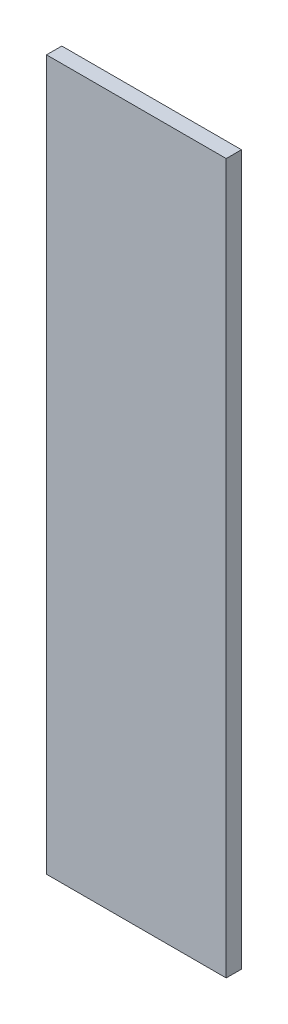
SolidWorks part; units mm, degrees
material "ABS"
ref_plane "Front Plane" through (0, 0, 0) normal (0, 0, 1) x (1, 0, 0)
ref_plane "Top Plane" through (0, 0, 0) normal (0, 1, 0) x (1, 0, 0)
ref_plane "Right Plane" through (0, 0, 0) normal (1, 0, 0) x (0, 0, -1)
sketch "Sketch1" plane through (0, 0, 0) normal (0, 0, 1) x (1, 0, 0)
  line L1 (-10, -39.5) -> (10, -39.5)
  line L2 (-10, -39.5) -> (-10, 39.5)
  line L3 (-10, 39.5) -> (10, 39.5)
  line L4 (10, -39.5) -> (10, 39.5)
  line L5 (-10, -39.5) -> (10, 39.5) construction
  line L6 (-10, 39.5) -> (10, -39.5) construction
  point P0 (0, 0)
  dimension "D1" = 20
  dimension "D2" = 79
extrude "Boss-Extrude1" add sketch "Sketch1" along normal blind 1.7
equation "\"smallPulleyTeeth\"= 30"
equation "\"largePulleyTeeth\"= 30"
equation "\"eighthThick\"= 3.0mm"
equation "\"sixteenthThick\" = 1.7mm"
equation "\"quarterThick\"=6.0mm"
equation "\"OD\" = 145mm"
equation "\"puckAngle\" = 60.5deg"
equation "\"puckDiam\" = 76.5mm"
equation "\"puckDist\" = 85mm"
equation "\"scoopFillet\" = 5mm"
equation "\"axlePress\" = 5.9mm"
equation "\"press\" = 0.2mm"
equation "\"wheelClear\" = 0.3mm"
equation "\"10-32clear\" = 4.8mm"
equation "\"10-32tap\" = 4.45mm"
equation "\"6-32clear\" = 3.3mm"
equation "\"8-32clear\" = 4.0mm"
equation "\"4-40clear\" = 3.0mm"
equation "\"wheelHeight\" = 22mm"
equation "\"wheelWell\" = 65mm"
equation "\"ledSmall\" = 3.1mm"
equation "\"ledLarge\" = 4.2mm"
equation "\"ledLength\" = 4.2mm"
equation "\"4-40close\" = 2.7mm"
equation "\"4-40nutThick\" = 2.2mm"
equation "\"4-40nutWidth\" = 6.2mm"
equation "\"4-40insertHeight\" = 3.5mm"
equation "\"4-40insert\" = 4mm"
equation "\"D1@Boss-Extrude1\"=\"sixteenthThick\""
